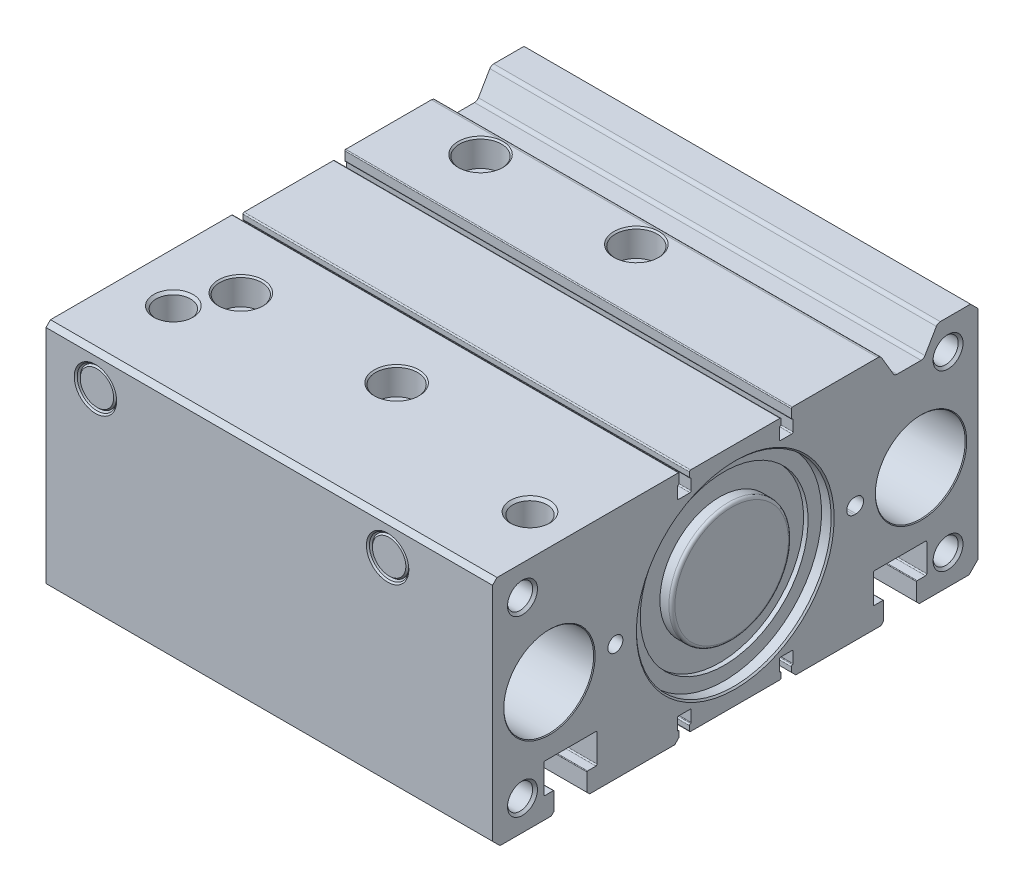
SolidWorks part; units mm, degrees
ref_plane "前视基准面" through (0, 0, 0) normal (0, 0, 1) x (1, 0, 0)
ref_plane "上视基准面" through (0, 0, 0) normal (0, 1, 0) x (1, 0, 0)
ref_plane "右视基准面" through (0, 0, 0) normal (1, 0, 0) x (0, 0, -1)
sketch "草图1" plane through (0, 0, 0) normal (1, 0, 0) x (0, 0, -1)
  line L0 (-81, 37.5) -> (-81, -36.5)
  line L1 (-81, -36.5) -> (-78.5, -39)
  line L2 (-78.5, -39) -> (-61.4, -39)
  line L3 (-61.4, -39) -> (-60.5, -38.1)
  line L4 (-60.5, -38.1) -> (-60.5, -32.2)
  line L5 (-60.7, -32) -> (-63.5, -32)
  line L6 (-63.9, -31.6) -> (-63.9, -22.4)
  line L7 (-63.5, -22) -> (-46.5, -22)
  line L8 (-46.1, -22.4) -> (-46.1, -31.6)
  line L9 (-46.5, -32) -> (-49.3, -32)
  line L10 (-49.5, -32.2) -> (-49.5, -38.1)
  line L11 (-49.5, -38.1) -> (-48.6, -39)
  line L12 (-48.6, -39) -> (-20.2, -39)
  line L13 (-20.2, -39) -> (-18.7, -37.5)
  line L14 (-18.7, -37.5) -> (-18.7, -35.9)
  line L15 (-19.3, -35.3) -> (-19.3, -31.7)
  line L16 (-18.9, -31.3) -> (-15.1, -31.3)
  line L17 (-14.7, -31.7) -> (-14.7, -35.3)
  line L18 (-15.3, -35.9) -> (-15.3, -37.4)
  line L19 (-14.9, -37.8) -> (14.9, -37.8)
  line L20 (15.3, -37.4) -> (15.3, -35.9)
  line L21 (14.7, -35.3) -> (14.7, -31.7)
  line L22 (15.1, -31.3) -> (18.9, -31.3)
  line L23 (19.3, -31.7) -> (19.3, -35.3)
  line L24 (18.7, -35.9) -> (18.7, -37.5)
  line L25 (18.7, -37.5) -> (20.2, -39)
  line L26 (20.2, -39) -> (48.6, -39)
  line L27 (48.6, -39) -> (49.5, -38.1)
  line L28 (49.5, -38.1) -> (49.5, -32.2)
  line L29 (49.3, -32) -> (46.5, -32)
  line L30 (46.1, -31.6) -> (46.1, -22.4)
  line L31 (46.5, -22) -> (63.5, -22)
  line L32 (63.9, -22.4) -> (63.9, -31.6)
  line L33 (63.5, -32) -> (60.7, -32)
  line L34 (60.5, -32.2) -> (60.5, -38.1)
  line L35 (60.5, -38.1) -> (61.4, -39)
  line L36 (61.4, -39) -> (78, -39)
  line L37 (78, -39) -> (81, -36)
  line L38 (81, -36) -> (81, 36.5)
  line L39 (81, 36.5) -> (78.5, 39)
  line L40 (78.5, 39) -> (68.4, 39)
  line L41 (67.1052, 38.2573) -> (63.2948, 31.7427)
  line L42 (62, 31) -> (54, 31)
  line L43 (52.7052, 31.7427) -> (48.8948, 38.2573)
  line L44 (47.6, 39) -> (19, 39)
  line L45 (18.7, 38.7) -> (18.7, 35.9)
  line L46 (19.3, 35.3) -> (19.3, 31.7)
  line L47 (18.9, 31.3) -> (15.1, 31.3)
  line L48 (14.7, 31.7) -> (14.7, 35.3)
  line L49 (15.3, 35.9) -> (15.3, 37.4)
  line L50 (14.9, 37.8) -> (-14.9, 37.8)
  line L51 (-15.3, 37.4) -> (-15.3, 35.9)
  line L52 (-14.7, 35.3) -> (-14.7, 31.7)
  line L53 (-15.1, 31.3) -> (-18.9, 31.3)
  line L54 (-19.3, 31.7) -> (-19.3, 35.3)
  line L55 (-18.7, 35.9) -> (-18.7, 38.7)
  line L56 (-19, 39) -> (-79.5, 39)
  line L57 (-79.5, 39) -> (-81, 37.5)
  arc A0 (-60.5, -32.2) -> (-60.7, -32) centre (-60.7, -32.2) ccw
  arc A1 (-63.5, -32) -> (-63.9, -31.6) centre (-63.5, -31.6) cw
  arc A2 (-63.9, -22.4) -> (-63.5, -22) centre (-63.5, -22.4) cw
  arc A3 (-46.5, -22) -> (-46.1, -22.4) centre (-46.5, -22.4) cw
  arc A4 (-46.1, -31.6) -> (-46.5, -32) centre (-46.5, -31.6) cw
  arc A5 (-49.3, -32) -> (-49.5, -32.2) centre (-49.3, -32.2) ccw
  arc A6 (-18.7, -35.9) -> (-19.1, -35.5) centre (-19.1, -35.9) ccw
  arc A7 (-19.1, -35.5) -> (-19.3, -35.3) centre (-19.1, -35.3) cw
  arc A8 (-19.3, -31.7) -> (-18.9, -31.3) centre (-18.9, -31.7) cw
  arc A9 (-15.1, -31.3) -> (-14.7, -31.7) centre (-15.1, -31.7) cw
  arc A10 (-14.7, -35.3) -> (-14.9, -35.5) centre (-14.9, -35.3) cw
  arc A11 (-14.9, -35.5) -> (-15.3, -35.9) centre (-14.9, -35.9) ccw
  arc A12 (-15.3, -37.4) -> (-14.9, -37.8) centre (-14.9, -37.4) ccw
  arc A13 (14.9, -37.8) -> (15.3, -37.4) centre (14.9, -37.4) ccw
  arc A14 (15.3, -35.9) -> (14.9, -35.5) centre (14.9, -35.9) ccw
  arc A15 (14.9, -35.5) -> (14.7, -35.3) centre (14.9, -35.3) cw
  arc A16 (14.7, -31.7) -> (15.1, -31.3) centre (15.1, -31.7) cw
  arc A17 (18.9, -31.3) -> (19.3, -31.7) centre (18.9, -31.7) cw
  arc A18 (19.3, -35.3) -> (19.1, -35.5) centre (19.1, -35.3) cw
  arc A19 (19.1, -35.5) -> (18.7, -35.9) centre (19.1, -35.9) ccw
  arc A20 (49.5, -32.2) -> (49.3, -32) centre (49.3, -32.2) ccw
  arc A21 (46.5, -32) -> (46.1, -31.6) centre (46.5, -31.6) cw
  arc A22 (46.1, -22.4) -> (46.5, -22) centre (46.5, -22.4) cw
  arc A23 (63.5, -22) -> (63.9, -22.4) centre (63.5, -22.4) cw
  arc A24 (63.9, -31.6) -> (63.5, -32) centre (63.5, -31.6) cw
  arc A25 (60.7, -32) -> (60.5, -32.2) centre (60.7, -32.2) ccw
  arc A26 (68.4, 39) -> (67.1052, 38.2573) centre (68.4, 37.5) ccw
  arc A27 (63.2948, 31.7427) -> (62, 31) centre (62, 32.5) cw
  arc A28 (54, 31) -> (52.7052, 31.7427) centre (54, 32.5) cw
  arc A29 (48.8948, 38.2573) -> (47.6, 39) centre (47.6, 37.5) ccw
  arc A30 (19, 39) -> (18.7, 38.7) centre (19, 38.7) ccw
  arc A31 (18.7, 35.9) -> (19.1, 35.5) centre (19.1, 35.9) ccw
  arc A32 (19.1, 35.5) -> (19.3, 35.3) centre (19.1, 35.3) cw
  arc A33 (19.3, 31.7) -> (18.9, 31.3) centre (18.9, 31.7) cw
  arc A34 (15.1, 31.3) -> (14.7, 31.7) centre (15.1, 31.7) cw
  arc A35 (14.7, 35.3) -> (14.9, 35.5) centre (14.9, 35.3) cw
  arc A36 (14.9, 35.5) -> (15.3, 35.9) centre (14.9, 35.9) ccw
  arc A37 (15.3, 37.4) -> (14.9, 37.8) centre (14.9, 37.4) ccw
  arc A38 (-14.9, 37.8) -> (-15.3, 37.4) centre (-14.9, 37.4) ccw
  arc A39 (-15.3, 35.9) -> (-14.9, 35.5) centre (-14.9, 35.9) ccw
  arc A40 (-14.9, 35.5) -> (-14.7, 35.3) centre (-14.9, 35.3) cw
  arc A41 (-14.7, 31.7) -> (-15.1, 31.3) centre (-15.1, 31.7) cw
  arc A42 (-18.9, 31.3) -> (-19.3, 31.7) centre (-18.9, 31.7) cw
  arc A43 (-19.3, 35.3) -> (-19.1, 35.5) centre (-19.1, 35.3) cw
  arc A44 (-19.1, 35.5) -> (-18.7, 35.9) centre (-19.1, 35.9) ccw
  arc A45 (-18.7, 38.7) -> (-19, 39) centre (-19, 38.7) ccw
extrude "凸台-拉伸1" add sketch "草图1" along normal blind 149
ref_plane "基准面1" through (0, 0, 40) normal (0, 0, 1) x (1, 0, 0)
sketch "草图2" plane through (0, 0, 40) normal (0, 0, 1) x (1, 0, 0)
  line L0 (24, 39) -> (31.5, 39)
  line L1 (31.5, 39) -> (31, 38.5)
  line L2 (31, 38.5) -> (31, 30)
  line L3 (31, 30) -> (28.25, 30)
  line L4 (28.25, 30) -> (28.25, -20)
  line L5 (28.25, -20) -> (29, -20)
  line L6 (29, -20) -> (28.188, -20.812)
  line L7 (28.188, -20.812) -> (28.188, -39.188)
  line L8 (28.188, -39.188) -> (29, -40)
  line L9 (29, -40) -> (24, -40)
  line L10 (24, -40) -> (24, 39)
  line L11 (24, -40) -> (24, 39) construction
revolve "切除-旋转1" cut sketch "草图2" angle 360 about L11 reverse direction yes
cosmetic thread "装饰螺纹线1" parameters "D1"=19, "D2"=10
ref_plane "基准面2" through (0, -40, 0) normal (0, 1, 0) x (1, 0, 0)
sketch "草图3" plane through (0, -40, 0) normal (0, 1, 0) x (1, 0, 0)
  line L0 (24, -40) -> (76, -40)
  line L1 (24, -40) -> (24, 40)
pattern_linear "阵列(线性)1" count 2 spacing 52 along (1, 0, 0) count 2 spacing 80 along (0, 0, -1) of "切除-旋转1"
ref_plane "基准面3" through (0, 0, 62) normal (0, 0, 1) x (1, 0, 0)
sketch "草图4" plane through (0, 0, 62) normal (0, 0, 1) x (1, 0, 0)
  line L0 (0, 0) -> (0, 16.25)
  line L1 (0, 16.25) -> (0.25, 16)
  line L2 (0.25, 16) -> (1.5, 16)
  line L3 (1.5, 16) -> (1.5, 10)
  line L4 (1.5, 10) -> (99, 10)
  line L5 (99, 10) -> (99, 15)
  line L6 (99, 15) -> (148.75, 15)
  line L7 (148.75, 15) -> (149, 15.25)
  line L8 (149, 15.25) -> (149, 0)
  line L9 (149, 0) -> (0, 0)
  line L10 (149, 0) -> (0, 0) construction
revolve "切除-旋转2" cut sketch "草图4" angle 360 about L10 reverse direction yes
ref_plane "基准面4" through (0, 0, -62) normal (0, 0, 1) x (1, 0, 0)
sketch "草图5" plane through (0, 0, -62) normal (0, 0, 1) x (1, 0, 0)
  line L0 (0, 0) -> (0, 16.25)
  line L1 (0, 16.25) -> (0.25, 16)
  line L2 (0.25, 16) -> (1.5, 16)
  line L3 (1.5, 16) -> (1.5, 10)
  line L4 (1.5, 10) -> (99, 10)
  line L5 (99, 10) -> (99, 15)
  line L6 (99, 15) -> (148.75, 15)
  line L7 (148.75, 15) -> (149, 15.25)
  line L8 (149, 15.25) -> (149, 0)
  line L9 (149, 0) -> (0, 0)
  line L10 (149, 0) -> (0, 0) construction
revolve "切除-旋转3" cut sketch "草图5" angle 360 about L10 reverse direction yes
sketch "草图6" plane through (0, 0, 0) normal (0, 0, 1) x (1, 0, 0)
  line L0 (0, 0) -> (0, 32.75)
  line L1 (0, 32.75) -> (0.25, 32.5)
  line L2 (0.25, 32.5) -> (3.7, 32.5)
  line L3 (3.7, 32.5) -> (3.7, 28)
  line L4 (3.7, 28) -> (5.2, 28)
  line L5 (5.2, 28) -> (5.2, 10)
  line L6 (5.2, 10) -> (17.5, 10)
  line L7 (17.5, 10) -> (17.5, 31.5)
  line L8 (17.5, 31.5) -> (141, 31.5)
  line L9 (141, 31.5) -> (141, 0)
  line L10 (141, 0) -> (0, 0)
  line L11 (141, 0) -> (0, 0) construction
revolve "切除-旋转4" cut sketch "草图6" angle 360 about L11 reverse direction yes
sketch "草图7" plane through (0, 0, 0) normal (0, 0, 1) x (1, 0, 0)
  line L0 (143.8, 0) -> (143.8, 28)
  line L1 (143.8, 28) -> (145.3, 28)
  line L2 (145.3, 28) -> (145.3, 32.5)
  line L3 (145.3, 32.5) -> (148.5, 32.5)
  line L4 (148.5, 32.5) -> (149, 33)
  line L5 (149, 33) -> (149, 0)
  line L6 (149, 0) -> (143.8, 0)
  line L7 (149, 0) -> (143.8, 0) construction
revolve "切除-旋转5" cut sketch "草图7" angle 360 about L7 reverse direction yes
sketch "草图8" plane through (0, 0, 0) normal (0, 0, 1) x (1, 0, 0)
  line L0 (143.8, 0) -> (143.8, 19.95)
  line L1 (143.8, 19.95) -> (146.8, 19.95)
  line L2 (147.8, 18.95) -> (147.8, 0)
  line L3 (147.8, 0) -> (143.8, 0)
  line L4 (147.8, 0) -> (143.8, 0) construction
  arc A0 (146.8, 19.95) -> (147.8, 18.95) centre (146.8, 18.95) cw
revolve "旋转1" add sketch "草图8" angle 360 about L4 reverse direction yes
ref_plane "基准面5" through (146.3, 0, 0) normal (1, 0, 0) x (0, 0, -1)
ref_plane "基准面6" through (2.7, 0, 0) normal (1, 0, 0) x (0, 0, -1)
sketch "草图9" plane through (0, 0, 0) normal (0, 0, 1) x (1, 0, 0)
  line L0 (1.2, 10) -> (6.2, 10)
  line L1 (6.2, 10) -> (6.2, 19.95)
  line L2 (6.2, 19.95) -> (1.95, 19.95)
  line L3 (1.2, 19.2) -> (1.2, 10)
  line L4 (6.2, 0) -> (1.2, 0) construction
  arc A0 (1.95, 19.95) -> (1.2, 19.2) centre (1.95, 19.2) ccw
revolve "旋转2" add sketch "草图9" angle 360 about L4 reverse direction yes
ref_plane "基准面7" through (0, 0, 55) normal (0, 0, 1) x (1, 0, 0)
hole_wizard "孔1" positions "草图11" profile "草图10" legacy
sketch "草图11" plane through (0, 39, 0) normal (0, 1, 0) x (1, 0, 0)
  point P0 (16.5, -55)
sketch "草图10" plane through (16.5, 39, 55) normal (1, 0, 0) x (0, 0, 1)
  line L0 (0, 0) -> (0, 13.05)
  line L1 (0, 13.05) -> (5.7225, 13.05)
  line L2 (5.7225, 13.05) -> (5.7225, 0.856)
  line L3 (5.7225, 0.856) -> (6.5785, 0)
  line L4 (6.5785, 0) -> (0, 0)
  line L5 (0, -6.4453) -> (0, 115.525) construction
  line L6 (-5.7225, 0.856) -> (-6.5785, 0) construction
  dimension "直径" = 11.445
  dimension "深度" = 13.05
  dimension "锥坑角度" = 90
  dimension "锥坑直径" = 13.157
cosmetic thread "装饰螺纹线2" parameters "D1"=12, "D2"=13.157
hole_wizard "孔2" positions "草图13" profile "草图12" legacy
sketch "草图13" plane through (0, 39, 0) normal (0, 1, 0) x (1, 0, 0)
  point P0 (135.5, -55)
sketch "草图12" plane through (135.5, 39, 55) normal (1, 0, 0) x (0, 0, 1)
  line L0 (0, 0) -> (0, 13.05)
  line L1 (0, 13.05) -> (5.7225, 13.05)
  line L2 (5.7225, 13.05) -> (5.7225, 0.856)
  line L3 (5.7225, 0.856) -> (6.5785, 0)
  line L4 (6.5785, 0) -> (0, 0)
  line L5 (0, -6.4453) -> (0, 115.525) construction
  line L6 (-5.7225, 0.856) -> (-6.5785, 0) construction
  dimension "直径" = 11.445
  dimension "深度" = 13.05
  dimension "锥坑角度" = 90
  dimension "锥坑直径" = 13.157
cosmetic thread "装饰螺纹线3" parameters "D1"=12, "D2"=13.157
ref_plane "基准面8" through (16.5, 0, 0) normal (1, 0, 0) x (0, 0, -1)
sketch "草图14" plane through (16.5, 0, 0) normal (1, 0, 0) x (0, 0, -1)
  line L0 (-81, 28) -> (-81, 35.0785)
  line L1 (-81, 35.0785) -> (-80.5, 34.5785)
  line L2 (-80.5, 34.5785) -> (-76.5, 34.5785)
  line L3 (-76.5, 34.5785) -> (-76.5, 34.0785)
  line L4 (-76.5, 34.0785) -> (-80, 34.0785)
  line L5 (-80, 34.0785) -> (-80.5, 33.5785)
  line L6 (-80.5, 33.5785) -> (-80.5, 28)
  line L7 (-80.5, 28) -> (-81, 28)
  line L8 (-76.5, 28) -> (-81, 28) construction
revolve "切除-旋转6" cut sketch "草图14" angle 360 about L8 reverse direction yes
ref_plane "基准面9" through (114, 0, 0) normal (1, 0, 0) x (0, 0, -1)
sketch "草图15" plane through (114, 0, 0) normal (1, 0, 0) x (0, 0, -1)
  line L0 (-81, 28) -> (-81, 35.0785)
  line L1 (-81, 35.0785) -> (-80.5, 34.5785)
  line L2 (-80.5, 34.5785) -> (-76.5, 34.5785)
  line L3 (-76.5, 34.5785) -> (-76.5, 34.0785)
  line L4 (-76.5, 34.0785) -> (-80, 34.0785)
  line L5 (-80, 34.0785) -> (-80.5, 33.5785)
  line L6 (-80.5, 33.5785) -> (-80.5, 28)
  line L7 (-80.5, 28) -> (-81, 28)
  line L8 (-76.5, 28) -> (-81, 28) construction
revolve "切除-旋转7" cut sketch "草图15" angle 360 about L8 reverse direction yes
ref_plane "基准面10" through (135.5, 0, 0) normal (1, 0, 0) x (0, 0, -1)
ref_plane "基准面11" through (0, 0, 40) normal (0, 0, 1) x (1, 0, 0)
sketch "草图16" plane through (0, 0, 40) normal (0, 0, 1) x (1, 0, 0)
  line L0 (50, -32) -> (52.5, -32)
  line L1 (52.5, -32) -> (52.5, -40)
  line L2 (52.5, -40) -> (50, -40)
  line L3 (50, -40) -> (50, -32)
  line L4 (50, -40) -> (50, -32) construction
revolve "切除-旋转8" cut sketch "草图16" angle 360 about L4 reverse direction yes
ref_plane "基准面12" through (0, 0, -40) normal (0, 0, 1) x (1, 0, 0)
sketch "草图17" plane through (0, 0, -40) normal (0, 0, 1) x (1, 0, 0)
  line L0 (50, -30.5566) -> (52.5, -32)
  line L1 (52.5, -32) -> (52.5, -40)
  line L2 (52.5, -40) -> (50, -40)
  line L3 (50, -40) -> (50, -30.5566)
  line L4 (50, -40) -> (50, -30.5566) construction
revolve "切除-旋转9" cut sketch "草图17" angle 360 about L4 reverse direction yes
ref_plane "基准面13" through (0, 0, 71) normal (0, 0, 1) x (1, 0, 0)
hole_wizard "孔3" positions "草图19" profile "草图18" legacy
sketch "草图19" plane through (149, 0, 0) normal (1, 0, 0) x (0, 0, -1)
  point P0 (-71, -29)
sketch "草图18" plane through (149, -29, 71) normal (0, 1, 0) x (0, 0, -1)
  line L0 (0, 0) -> (0, 28.8179)
  line L1 (0, 28.8179) -> (4.188, 26.4)
  line L2 (4.188, 26.4) -> (4.188, 0.812)
  line L3 (4.188, 0.812) -> (5, 0)
  line L4 (5, 0) -> (0, 0)
  line L5 (0, -14.3089) -> (0, 102.4216) construction
  line L6 (0, 28.8179) -> (-4.188, 26.4) construction
  line L7 (-4.188, 0.812) -> (-5, 0) construction
  dimension "直径" = 8.376
  dimension "深度" = 26.4
  dimension "锥坑直径" = 10
  dimension "锥坑角度" = 90
  dimension "导头角度" = 120
cosmetic thread "装饰螺纹线4" parameters "D1"=22, "D2"=10
ref_plane "基准面14" through (149, 0, 0) normal (1, 0, 0) x (0, 0, -1)
sketch "草图20" plane through (149, 0, 0) normal (1, 0, 0) x (0, 0, -1)
  line L0 (-71, -29) -> (71, -29)
  line L1 (-71, -29) -> (-71, 29)
pattern_linear "阵列(线性)2" count 2 spacing 142 along (0, 0, -1) count 2 spacing 58 along (0, 1, 0) of "孔3"
hole_wizard "孔4" positions "草图22" profile "草图21" legacy
sketch "草图22" plane through (149, 0, 0) normal (1, 0, 0) x (0, 0, -1)
  point P0 (-40, 0)
sketch "草图21" plane through (149, 0, 40) normal (0, 1, 0) x (0, 0, -1)
  line L0 (0, 0) -> (0, 8)
  line L1 (0, 8) -> (2.5, 8)
  line L2 (2.5, 8) -> (2.5, 0)
  line L3 (2.5, 0) -> (0, 0)
  line L4 (0, 110) -> (0, -10) construction
  dimension "直径" = 5
  dimension "深度" = 8
hole_wizard "孔5" positions "草图24" profile "草图23" legacy
sketch "草图24" plane through (149, 0, 0) normal (1, 0, 0) x (0, 0, -1)
  point P0 (40, 0)
sketch "草图23" plane through (149, 0, -40) normal (0, 1, 0) x (0, 0, -1)
  line L0 (0, 0) -> (0, 9.4434)
  line L1 (0, 9.4434) -> (2.5, 8)
  line L2 (2.5, 8) -> (2.5, 0)
  line L4 (2.5, 0) -> (0, 0)
  line L6 (0, 9.4434) -> (-2.5, 8) construction
  line L7 (0, -4.2442) -> (0, 117.3081) construction
  dimension "直径" = 5
  dimension "深度" = 8
  dimension "导头角度" = 120
ref_plane "基准面15" through (0, -39, 0) normal (0, 1, 0) x (1, 0, 0)
sketch "草图25" plane through (0, -39, 0) normal (0, 1, 0) x (1, 0, 0)
  line L0 (52.5, 39.7) -> (52.5, 40.3)
  line L1 (47.5, 40.3) -> (47.5, 39.7)
  arc A0 (47.5, 39.7) -> (52.5, 39.7) centre (50, 39.7) ccw
  arc A1 (52.5, 40.3) -> (47.5, 40.3) centre (50, 40.3) ccw
extrude "切除-拉伸1" cut sketch "草图25" along normal blind 4
ref_plane "基准面16" through (149, 0, 0) normal (1, 0, 0) x (0, 0, -1)
sketch "草图26" plane through (149, 0, 0) normal (1, 0, 0) x (0, 0, -1)
  line L0 (39.7, -2.5) -> (40.3, -2.5)
  line L1 (40.3, 2.5) -> (39.7, 2.5)
  arc A0 (39.7, 2.5) -> (39.7, -2.5) centre (39.7, 0) ccw
  arc A1 (40.3, -2.5) -> (40.3, 2.5) centre (40.3, 0) ccw
extrude "切除-拉伸2" cut sketch "草图26" against normal blind 4
ref_plane "基准面17" through (-28, 0, 0) normal (1, 0, 0) x (0, 0, -1)
ref_plane "基准面18" through (1, 0, 0) normal (1, 0, 0) x (0, 0, -1)
ref_plane "基准面19" through (148, 0, 0) normal (1, 0, 0) x (0, 0, -1)
ref_plane "IP_SWITCH1 XY" through (1, 0, 0) normal (-1, 0, 0) x (0, 0, 1)
ref_plane "IP_SWITCH1 XZ" through (0, 31.3, 0) normal (0, 1, 0) x (1, 0, 0)
ref_plane "IP_SWITCH1 YZ" through (0, 0, -17) normal (0, 0, -1) x (-1, 0, 0)
ref_axis "IP_SWITCH1 X" through (1, 31.3, 80.9) along (0, 0, -1)
ref_axis "IP_SWITCH1 Y" through (1, 50, -17) along (0, -1, 0)
ref_axis "IP_SWITCH1 Z" through (-80.9, 31.3, -17) along (1, 0, 0)
sketch3d "IP_SWITCH1"
  point P0 (1, 31.3, -17)
ref_plane "IP_SWITCH2 XY" through (148, 0, 0) normal (1, 0, 0) x (0, 0, -1)
ref_plane "IP_SWITCH2 XZ" through (0, -31.3, 0) normal (0, -1, 0) x (-1, 0, 0)
ref_plane "IP_SWITCH2 YZ" through (0, 0, 17) normal (0, 0, -1) x (-1, 0, 0)
ref_axis "IP_SWITCH2 X" through (148, -31.3, 80.9) along (0, 0, -1)
ref_axis "IP_SWITCH2 Y" through (148, -50, 17) along (0, 1, 0)
ref_axis "IP_SWITCH2 Z" through (80.9, -31.3, 17) along (-1, 0, 0)
sketch3d "IP_SWITCH2"
  point P0 (148, -31.3, 17)
ref_plane "for_dummy XY" through (0, 0, 0) normal (1, 0, 0) x (0, 0, -1)
ref_plane "for_dummy XZ" through (0, 0, 0) normal (0, -1, 0) x (-1, 0, 0)
ref_plane "for_dummy YZ" through (0, 0, 0) normal (0, 0, -1) x (-1, 0, 0)
ref_axis "for_dummy X" through (0, 0, 80.9) along (0, 0, -1)
ref_axis "for_dummy Y" through (0, -50, 0) along (0, 1, 0)
ref_axis "for_dummy Z" through (80.9, 0, 0) along (-1, 0, 0)
sketch3d "for_dummy"
  point P0 (0, 0, 0)
ref_plane "for_rod XY" through (-28, 0, 0) normal (-1, 0, 0) x (0, 0, 1)
ref_plane "for_rod XZ" through (0, 0, 0) normal (0, 1, 0) x (1, 0, 0)
ref_plane "for_rod YZ" through (0, 0, 0) normal (0, 0, -1) x (-1, 0, 0)
ref_axis "for_rod X" through (-28, 0, 80.9) along (0, 0, -1)
ref_axis "for_rod Y" through (-28, 50, 0) along (0, -1, 0)
ref_axis "for_rod Z" through (-80.9, 0, 0) along (1, 0, 0)
sketch3d "for_rod"
  point P0 (-28, 0, 0)
